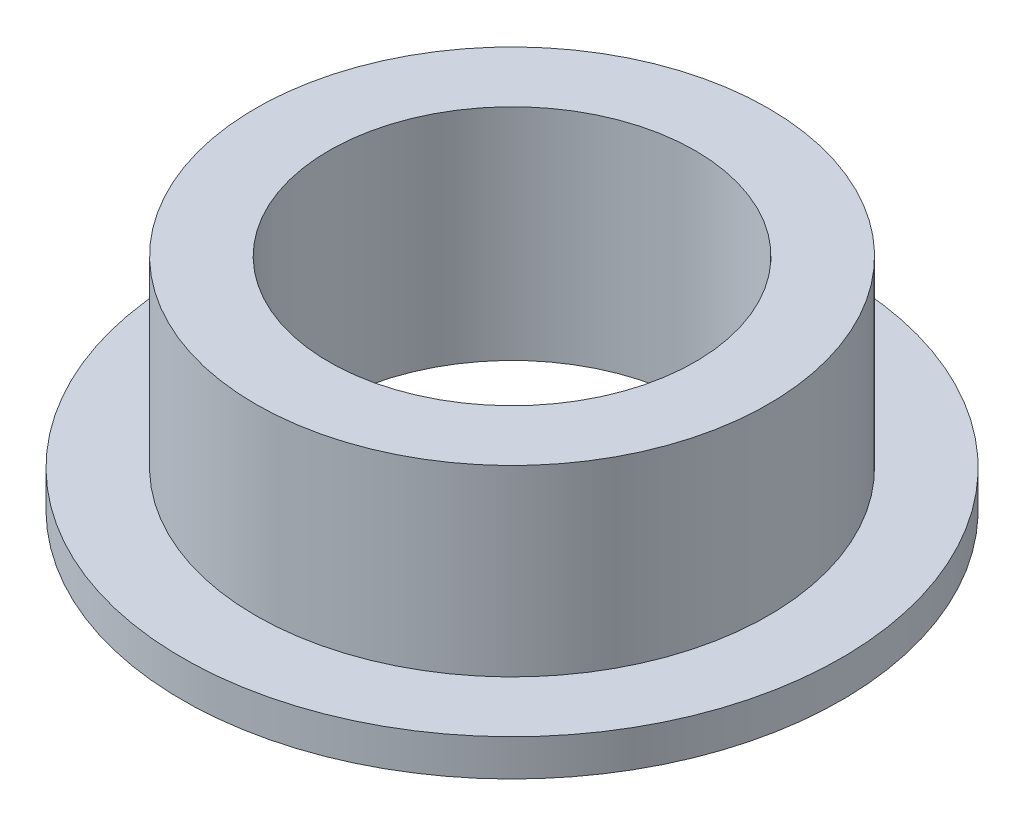
SolidWorks part; units mm, degrees
material "Alum Plate"
ref_plane "Front Plane" through (0, 0, 0) normal (0, 0, 1) x (1, 0, 0)
ref_plane "Top Plane" through (0, 0, 0) normal (0, 1, 0) x (1, 0, 0)
ref_plane "Right Plane" through (0, 0, 0) normal (1, 0, 0) x (0, 0, -1)
other "Bounding Box"
ref_plane "Default Plane" through (-8.9266, -12.7485, 0) normal (-0.1736, 0.9848, 0) x (0.9848, 0.1736, 0)
sketch "Sketch1" plane through (0, 0, 0) normal (0, 1, 0) x (1, 0, 0)
  circle A0 centre (0, 0) radius 7.9375
  circle A1 centre (0, 0) radius 11.1125
  dimension "D1" = 15.875
  dimension "D2" = 22.225
extrude "Boss-Extrude1" add sketch "Sketch1" along normal mid plane 9.525
sketch "Sketch2" plane through (0, -4.7625, 0) normal (0, -1, 0) x (1, 0, 0)
  circle A0 centre (0, 0) radius 14.2875
  circle A1 centre (0, 0) radius 11.1125 construction
  circle A2 centre (0, 0) radius 11.1125
  dimension "D1" = 28.575
extrude "Boss-Extrude2" add sketch "Sketch2" against normal blind 1.5875
